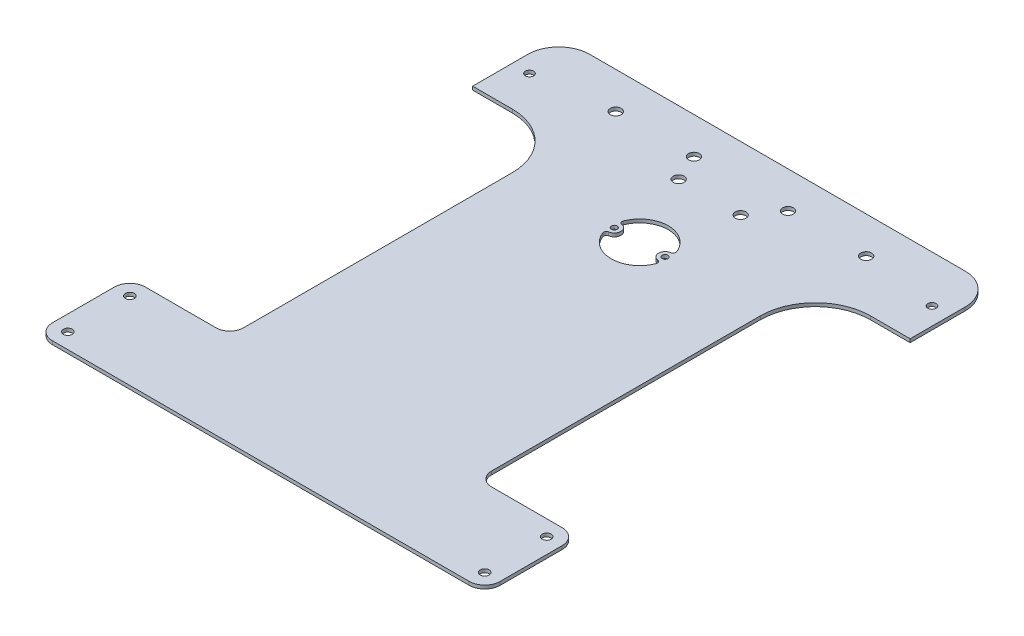
SolidWorks part; units mm, degrees
material "Thornel VCB-20 Carbon Cloth"
ref_plane "Front" through (0, 0, 0) normal (0, 0, 1) x (1, 0, 0)
ref_plane "Top" through (0, 0, 0) normal (0, 1, 0) x (1, 0, 0)
ref_plane "Right" through (0, 0, 0) normal (1, 0, 0) x (0, 0, -1)
ref_axis "X" through (-80.9, 0, 0) along (1, 0, 0)
ref_axis "Y" through (0, -50, 0) along (0, 1, 0)
ref_axis "Z" through (0, 0, -80.9) along (0, 0, 1)
sketch "Sketch1" plane through (0, 0, 0) normal (0, 1, 0) x (1, 0, 0)
  line L0 (-65, -150) -> (65, -150)
  line L1 (-65, -150) -> (-65, -123)
  line L2 (-65, -123) -> (-36, -123)
  line L3 (-36, -123) -> (-36, -25)
  line L4 (-36, -25) -> (-63.5, -25)
  line L5 (-63.5, -25) -> (-63.5, 0)
  line L6 (-63.5, 0) -> (63.5, 0)
  line L7 (63.5, 0) -> (63.5, -25)
  line L8 (63.5, -25) -> (36, -25)
  line L9 (36, -25) -> (36, -123)
  line L10 (36, -123) -> (65, -123)
  line L11 (65, -123) -> (65, -150)
  line L12 (0, -150) -> (0, 0) construction
  dimension "D1" = 130
  dimension "D2" = 72
  dimension "D5" = 25
  dimension "D6" = 127
  dimension "D7" = 150
  dimension "D3" = 27
  dimension "D4" = 90
extrude "Boss-Extrude1" add sketch "Sketch1" along normal mid plane 1
hole_wizard "M2 Clearance Hole1" positions "Sketch2" profile "Sketch3" hole size "M2" standard "ANSI Metric" end condition up to next
sketch "Sketch2" plane through (0, 0.5, 0) normal (0, 1, 0) x (1, 0, 0)
  line L0 (-60.5, -145.5) -> (60.5, -145.5) construction
  line L2 (-65, -150) -> (65, -150) construction
  line L3 (-65, -123) -> (-65, -150) construction
  line L4 (65, -150) -> (65, -123) construction
  line L5 (-60.5, -127.5) -> (-60.5, -145.5) construction
  line L8 (60.5, -127.5) -> (60.5, -145.5) construction
  point P0 (-60.5, -145.5)
  point P2 (60.5, -145.5)
  point P15 (-60.5, -127.5)
  point P17 (60.5, -127.5)
  point P48 (83.772, -145.5)
  point P49 (0, 0)
  point P50 (0, 0)
  point P51 (0, 0)
  point P52 (-99.7276, -145.5)
  point P53 (0, 0)
  dimension "D1" = 4.5
  dimension "D2" = 4.5
  dimension "D3" = 4.5
  dimension "D4" = 18
sketch "Sketch3" plane through (-60.5, 0.5, 145.5) normal (1, 0, 0) x (0, 0, 1)
  line L0 (0, 0) -> (0, 1)
  line L1 (0, 1) -> (1.3, 1)
  line L2 (1.3, 1) -> (1.3, 0)
  line L5 (1.3, 0) -> (0, 0)
  line L11 (0, -6.35) -> (0, 107.95) construction
  dimension "Thru Hole Dia." = 2.6
  dimension "Thru Hole Depth" = 1
fillet "Fillet1" radius 4.5 4 edges at (65, 0, 150) (-65, 0, 150) (65, 0, 123) (-65, 0, 123)
fillet "Fillet2" radius 9 2 edges at (63.5, 0, 0) (-63.5, 0, 0)
hole_wizard "M2 Clearance Hole2" positions "Sketch7" profile "Sketch8" hole size "M2" standard "ANSI Metric" end condition up to next
sketch "Sketch7" plane through (0, 0.5, 0) normal (0, 1, 0) x (1, 0, 0)
  line L0 (-58.42, -13.57) -> (58.42, -13.57) construction
  line L2 (0, 0) -> (0, -13.57) construction
  line L3 (54.5, 0) -> (-54.5, 0) construction
  line L5 (-63.5, -25) -> (-36, -25) construction
  point P0 (-58.42, -13.57)
  point P2 (58.42, -13.57)
  dimension "D1" = 116.84
  dimension "D2" = 11.43
sketch "Sketch8" plane through (-58.42, 0.5, 13.57) normal (1, 0, 0) x (0, 0, 1)
  line L0 (0, 0) -> (0, 1)
  line L1 (0, 1) -> (1.2, 1)
  line L2 (1.2, 1) -> (1.2, 0)
  line L5 (1.2, 0) -> (0, 0)
  line L11 (0, -6.35) -> (0, 107.95) construction
  dimension "Thru Hole Dia." = 2.4
  dimension "Thru Hole Depth" = 1
fillet "Fillet4" radius 4 2 edges at (36, 0, 123) (-36, 0, 123)
fillet "Fillet5" radius 16 2 edges at (36, 0, 25) (-36, 0, 25)
sketch "Sketch13" plane through (0, 0.5, 0) normal (0, 1, 0) x (1, 0, 0)
  line L0 (-38, -131) -> (-38, -142) construction
  line L1 (-35, -131) -> (-35, -142)
  line L3 (38, -131) -> (38, -142) construction
  line L5 (35, -131) -> (35, -142)
  line L6 (-38, -136.5) -> (38, -136.5) construction
  line L7 (0, -136.5) -> (0, 0) construction
  line L8 (54.5, 0) -> (-54.5, 0) construction
  line L11 (-60.5, -127.5) -> (-60.5, -145.5) construction
  line L12 (-60.5, -136.5) -> (-38, -136.5) construction
  line L13 (-38, -128) -> (-45.5, -128)
  line L14 (-38, -145) -> (-45.5, -145)
  line L15 (38, -128) -> (45.5, -128)
  line L16 (38, -145) -> (45.5, -145)
  line L17 (48.5, -131) -> (48.5, -142)
  line L18 (-48.5, -131) -> (-48.5, -142)
  line L19 (-35, -136.5) -> (-48.5, -136.5) construction
  line L20 (35, -136.5) -> (48.5, -136.5) construction
  arc A0 (-35, -131) -> (-38, -128) centre (-38, -131) ccw
  arc A1 (-38, -145) -> (-35, -142) centre (-38, -142) ccw
  arc A2 (38, -128) -> (35, -131) centre (38, -131) ccw
  arc A3 (35, -142) -> (38, -145) centre (38, -142) ccw
  circle A4 centre (-60.5, -127.5) radius 1.3 construction
  arc A5 (45.5, -128) -> (48.5, -131) centre (45.5, -131) cw
  arc A6 (48.5, -142) -> (45.5, -145) centre (45.5, -142) cw
  arc A7 (-45.5, -128) -> (-48.5, -131) centre (-45.5, -131) ccw
  arc A8 (-48.5, -142) -> (-45.5, -145) centre (-45.5, -142) ccw
  point P2 (-38, -136.5)
  point P8 (38, -136.5)
  dimension "D5" = 3.5
  dimension "D1" = 17
  dimension "D2" = 13.5
  dimension "D3" = 70
extrude "Cut-Extrude4" [suppressed] cut sketch "Sketch13" against normal through all
hole_wizard "M1.6 Clearance Hole1" positions "Sketch14" profile "Sketch15" hole size "M1.6" standard "ANSI Metric" end condition up to next
sketch "Sketch14" plane through (0, 0.5, 0) normal (0, 1, 0) x (1, 0, 0)
  line L2 (-7.366, -40) -> (7.366, -40) construction
  line L3 (0, 0) -> (0, -40) construction
  line L4 (54.5, 0) -> (-54.5, 0) construction
  point P0 (-7.366, -40)
  point P2 (7.366, -40)
  dimension "D1" = 14.732
  dimension "D2" = 40
sketch "Sketch15" plane through (-7.366, 0.5, 40) normal (1, 0, 0) x (0, 0, 1)
  line L0 (0, 0) -> (0, 1)
  line L1 (0, 1) -> (0.85, 1)
  line L2 (0.85, 1) -> (0.85, 0)
  line L5 (0.85, 0) -> (0, 0)
  line L11 (0, -6.35) -> (0, 107.95) construction
  dimension "Thru Hole Dia." = 1.7
  dimension "Thru Hole Depth" = 1
sketch "Sketch17" plane through (0, 0.5, 0) normal (0, 1, 0) x (1, 0, 0)
  line L0 (-36.35, -10.6) -> (-13.65, -10.6) construction
  line L1 (-13.65, -10.6) -> (13.65, -10.6) construction
  line L2 (13.65, -10.6) -> (36.35, -10.6) construction
  line L3 (7.8, -18.5) -> (-10.2, -18.5) construction
  line L4 (0, -10.6) -> (0, 0) construction
  line L5 (-25, -10.6) -> (-25, -15.252) construction
  line L6 (0, -10.6) -> (0, -18.5) construction
  line L7 (54.5, 0) -> (-54.5, 0) construction
  line L8 (25, -10.6) -> (25, -14.0507) construction
  circle A2 centre (7.8, -18.5) radius 1.575
  circle A3 centre (-10.2, -18.5) radius 1.575
  circle A8 centre (36.35, -10.6) radius 1.575
  circle A9 centre (13.65, -10.6) radius 1.575
  circle A10 centre (-13.65, -10.6) radius 1.575
  circle A11 centre (-36.35, -10.6) radius 1.575
  point P22 (-1.2, -18.5)
  dimension "D7" = 3.15
  dimension "D1" = 22.7
  dimension "D2" = 50
  dimension "D4" = 10.6
  dimension "D5" = 18.5
  dimension "D6" = 1.2
  dimension "D8" = 18
extrude "Cut-Extrude6" cut sketch "Sketch17" against normal through all
sketch "Sketch18" plane through (0, 0.5, 0) normal (0, 1, 0) x (1, 0, 0)
  line L0 (-7.366, -40) -> (7.366, -40) construction
  arc A0 (8.1142, -38.2535) -> (-8.1142, -38.2535) centre (0, -40) ccw
  arc A1 (-8.1142, -41.7465) -> (-8.1142, -38.2535) centre (-7.366, -40) ccw
  arc A2 (8.1142, -38.2535) -> (8.1142, -41.7465) centre (7.366, -40) ccw
  arc A3 (-8.1142, -41.7465) -> (8.1142, -41.7465) centre (0, -40) ccw
  circle A6 centre (-7.366, -40) radius 0.85 construction
  circle A8 centre (7.366, -40) radius 0.85 construction
  point P1 (0, 0)
  point P11 (0, 0)
  dimension "D2" = 3.8
  dimension "D3" = 16.6
extrude "Cut-Extrude7" cut sketch "Sketch18" against normal up to next
fillet "Fillet6" radius 0.8 4 edges at (-8.1142, 0, 41.7465) (-8.1142, 0, 38.2535) (8.1142, 0, 41.7465) (8.1142, 0, 38.2535)
equation "\"D1@Sketch1\"=92+38"
